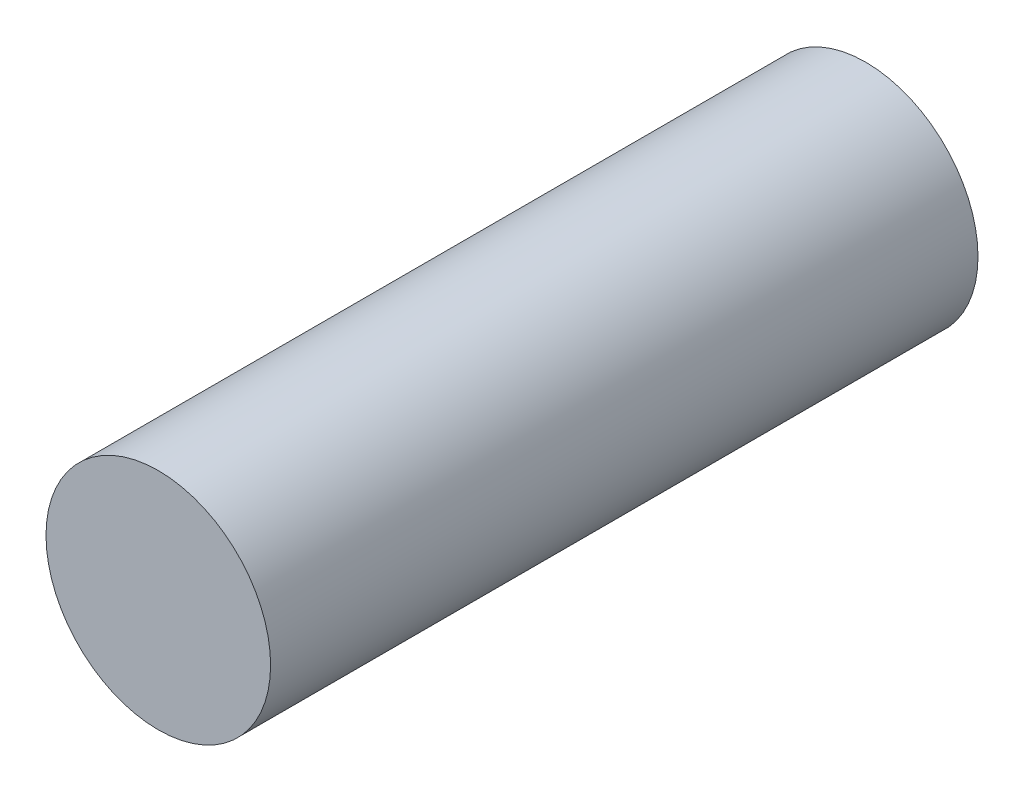
SolidWorks part; units mm, degrees
ref_plane "Front Plane" through (0, 0, 0) normal (0, 0, 1) x (1, 0, 0)
ref_plane "Top Plane" through (0, 0, 0) normal (0, 1, 0) x (1, 0, 0)
ref_plane "Right Plane" through (0, 0, 0) normal (1, 0, 0) x (0, 0, -1)
sketch "Sketch1" plane through (0, 0, 0) normal (0, 0, 1) x (1, 0, 0)
  line L1 (6.35, 3.6662) -> (0, 7.3323)
  line L2 (0, 7.3323) -> (-6.35, 3.6662)
  line L3 (-6.35, 3.6662) -> (-6.35, -3.6662)
  line L4 (-6.35, -3.6662) -> (0, -7.3323)
  line L5 (0, -7.3323) -> (6.35, -3.6662)
  line L6 (6.35, -3.6662) -> (6.35, 3.6662)
  circle A0 centre (0, 0) radius 6.35
  point P11 (0, 0)
  dimension "D1" = 12.7
extrude "Boss-Extrude1" add sketch "Sketch1" along normal mid plane 40 contours A0 region at (0, 0, 0)
ref_axis "Axis2" through (0, 0, 0) along (0, 0, 1)
